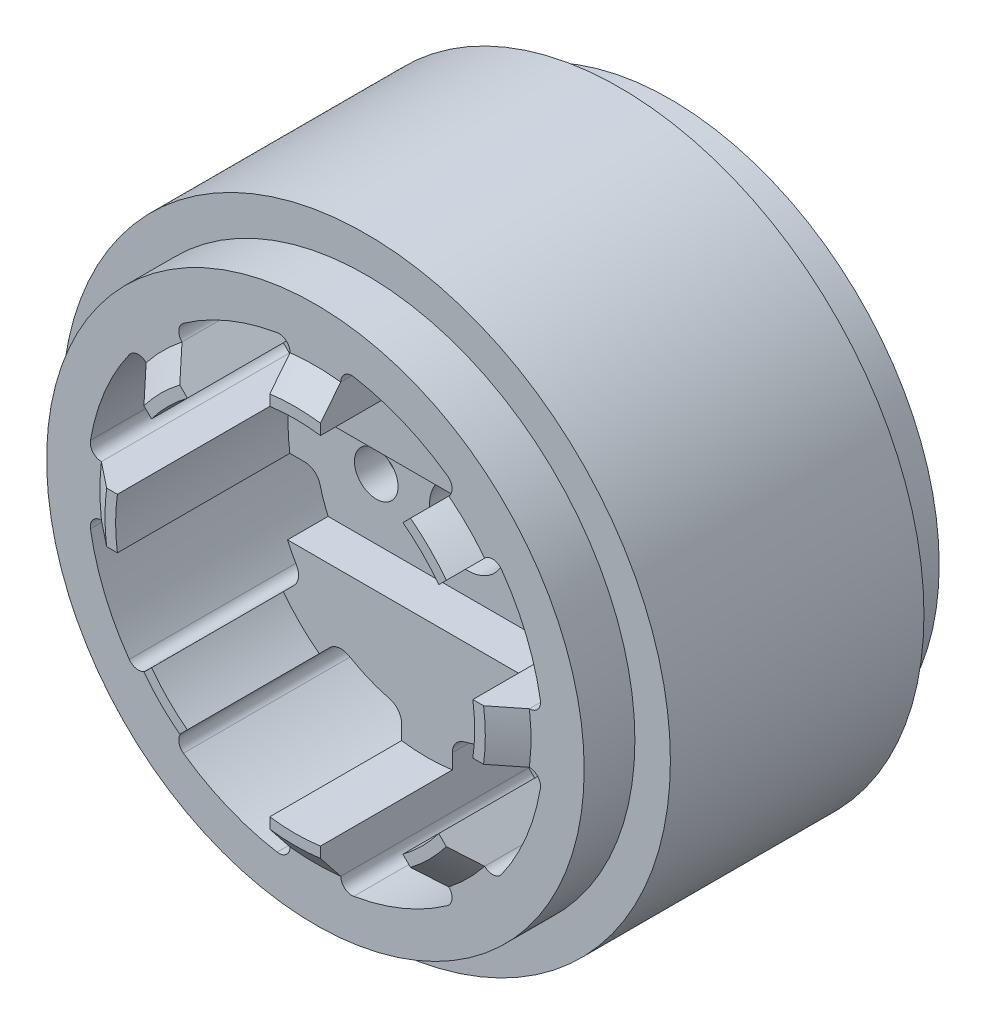
SolidWorks part; units mm, degrees
ref_plane "Front Plane" through (0, 0, 0) normal (0, 0, 1) x (1, 0, 0)
ref_plane "Top Plane" through (0, 0, 0) normal (0, 1, 0) x (1, 0, 0)
ref_plane "Right Plane" through (0, 0, 0) normal (1, 0, 0) x (0, 0, -1)
sketch "Sketch1" plane through (0, 0, 0) normal (0, 0, 1) x (1, 0, 0)
  line L0 (0, 0) -> (52.3745, 0) construction
  line L1 (0, 0) -> (0, 45.9782) construction
  line L2 (2.5, 21.1024) -> (2.5, 16.0565)
  line L3 (-13.7477, 6) -> (13.7477, 6)
  line L4 (-13.7477, -6) -> (13.7477, -6)
  line L5 (-2.5, 21.1024) -> (-2.5, 16.0565)
  line L6 (16.6894, 13.1539) -> (13.1215, 9.5859)
  line L7 (13.1539, 16.6894) -> (9.5859, 13.1215)
  line L8 (21.1024, -2.5) -> (16.0565, -2.5)
  line L9 (21.1024, 2.5) -> (16.0565, 2.5)
  line L10 (13.1539, -16.6894) -> (9.5859, -13.1215)
  line L11 (16.6894, -13.1539) -> (13.1215, -9.5859)
  line L12 (-2.5, -21.1024) -> (-2.5, -16.0565)
  line L13 (2.5, -21.1024) -> (2.5, -16.0565)
  line L14 (-16.6894, -13.1539) -> (-13.1215, -9.5859)
  line L15 (-13.1539, -16.6894) -> (-9.5859, -13.1215)
  line L16 (-21.1024, 2.5) -> (-16.0565, 2.5)
  line L17 (-21.1024, -2.5) -> (-16.0565, -2.5)
  line L18 (-13.1539, 16.6894) -> (-9.5859, 13.1215)
  line L19 (-16.6894, 13.1539) -> (-13.1215, 9.5859)
  circle A0 centre (0, 0) radius 3.75
  circle A1 centre (0, 0) radius 15
  circle A2 centre (0, 0) radius 22.5
  circle A3 centre (0, 0) radius 26.5
  circle A4 centre (9, 0) radius 3
  circle A5 centre (-9, 0) radius 3
  arc A6 (2.5, 21.1024) -> (3.7774, 22.1807) centre (3.5937, 21.1024) cw
  circle A7 centre (9, 0) radius 2.15
  circle A8 centre (-9, 0) radius 2.15
  arc A9 (-2.5, 21.1024) -> (-3.7774, 22.1807) centre (-3.5937, 21.1024) ccw
  arc A10 (16.6894, 13.1539) -> (18.3551, 13.0131) centre (17.4628, 12.3805) cw
  arc A11 (13.1539, 16.6894) -> (13.0131, 18.3551) centre (12.3805, 17.4628) ccw
  arc A12 (21.1024, -2.5) -> (22.1807, -3.7774) centre (21.1024, -3.5937) cw
  arc A13 (21.1024, 2.5) -> (22.1807, 3.7774) centre (21.1024, 3.5937) ccw
  arc A14 (13.1539, -16.6894) -> (13.0131, -18.3551) centre (12.3805, -17.4628) cw
  arc A15 (16.6894, -13.1539) -> (18.3551, -13.0131) centre (17.4628, -12.3805) ccw
  arc A16 (-2.5, -21.1024) -> (-3.7774, -22.1807) centre (-3.5937, -21.1024) cw
  arc A17 (2.5, -21.1024) -> (3.7774, -22.1807) centre (3.5937, -21.1024) ccw
  arc A18 (-16.6894, -13.1539) -> (-18.3551, -13.0131) centre (-17.4628, -12.3805) cw
  arc A19 (-13.1539, -16.6894) -> (-13.0131, -18.3551) centre (-12.3805, -17.4628) ccw
  arc A20 (-21.1024, 2.5) -> (-22.1807, 3.7774) centre (-21.1024, 3.5937) cw
  arc A21 (-21.1024, -2.5) -> (-22.1807, -3.7774) centre (-21.1024, -3.5937) ccw
  arc A22 (-13.1539, 16.6894) -> (-13.0131, 18.3551) centre (-12.3805, 17.4628) cw
  arc A23 (-16.6894, 13.1539) -> (-18.3551, 13.0131) centre (-17.4628, 12.3805) ccw
  circle A24 centre (0, 0) radius 30
  circle A25 centre (0, 0) radius 17.7
  circle A26 centre (0, 0) radius 21.25
  circle A27 centre (0, 0) radius 16.25
  arc A28 (2.5, 16.0565) -> (3.6792, 14.5418) centre (4.0625, 16.0565) ccw
  arc A29 (-2.5, 16.0565) -> (-3.6792, 14.5418) centre (-4.0625, 16.0565) cw
  arc A30 (13.1215, 9.5859) -> (12.8842, 7.681) centre (14.2263, 8.4811) ccw
  arc A31 (9.5859, 13.1215) -> (7.681, 12.8842) centre (8.4811, 14.2263) cw
  arc A32 (16.0565, -2.5) -> (14.5418, -3.6792) centre (16.0565, -4.0625) ccw
  arc A33 (16.0565, 2.5) -> (14.5418, 3.6792) centre (16.0565, 4.0625) cw
  arc A34 (9.5859, -13.1215) -> (7.681, -12.8842) centre (8.4811, -14.2263) ccw
  arc A35 (13.1215, -9.5859) -> (12.8842, -7.681) centre (14.2263, -8.4811) cw
  arc A36 (-2.5, -16.0565) -> (-3.6792, -14.5418) centre (-4.0625, -16.0565) ccw
  arc A37 (2.5, -16.0565) -> (3.6792, -14.5418) centre (4.0625, -16.0565) cw
  arc A38 (-13.1215, -9.5859) -> (-12.8842, -7.681) centre (-14.2263, -8.4811) ccw
  arc A39 (-9.5859, -13.1215) -> (-7.681, -12.8842) centre (-8.4811, -14.2263) cw
  arc A40 (-16.0565, 2.5) -> (-14.5418, 3.6792) centre (-16.0565, 4.0625) ccw
  arc A41 (-16.0565, -2.5) -> (-14.5418, -3.6792) centre (-16.0565, -4.0625) cw
  arc A42 (-9.5859, 13.1215) -> (-7.681, 12.8842) centre (-8.4811, 14.2263) ccw
  arc A43 (-13.1215, 9.5859) -> (-12.8842, 7.681) centre (-14.2263, 8.4811) cw
  point P87 (0, 0)
  point P138 (0, 0)
  dimension "D1" = 7.5
  dimension "D2" = 30
  dimension "D3" = 45
  dimension "D4" = 53
  dimension "D5" = 9
  dimension "D6" = 6
  dimension "D8" = 42.5
  dimension "D9" = 4.3
  dimension "D12" = 60
  dimension "D13" = 35.4
  dimension "D14" = 32.5
  dimension "D15" = 8
  dimension "D7" = 2.5
  dimension "D10" = 6
  dimension "D11" = 8
extrude "Boss-Extrude7" add sketch "Sketch1<15>" along normal blind 15 separate body contours A1
sketch "Sketch1<15>" plane through (0, 0, 0) normal (0, 0, 1) x (1, 0, 0) same geometry as "Sketch1"
extrude "Cut-Extrude2" cut sketch "Sketch1<16>" along normal blind 15 from surface contours A0 starting at face at (15, 0, 0)
sketch "Sketch1<16>" plane through (0, 0, 0) normal (0, 0, 1) x (1, 0, 0) same geometry as "Sketch1"
extrude "Cut-Extrude4" cut sketch "Sketch1<18>" along normal blind 12 from surface contours A5 | A4 starting at face at (3.75, 0, 0)
sketch "Sketch1<18>" plane through (0, 0, 0) normal (0, 0, 1) x (1, 0, 0) same geometry as "Sketch1"
extrude "Cut-Extrude5" cut sketch "Sketch1<19>" along normal blind 15 from surface contours A8 starting at face at (-6, 0, 0)
sketch "Sketch1<19>" plane through (0, 0, 0) normal (0, 0, 1) x (1, 0, 0) same geometry as "Sketch1"
extrude "Cut-Extrude6" cut sketch "Sketch1" along normal blind 15 from surface contours A7 starting at face at (-6, 0, 0)
extrude "Boss-Extrude12" add sketch "Sketch1<22>" along normal blind 4 from offset 15 contours L3 A1 | L4 A1 region at (0, 9.7124, 0) region at (0, -9.7124, 0)
sketch "Sketch1<22>" plane through (0, 0, 0) normal (0, 0, 1) x (1, 0, 0) same geometry as "Sketch1"
extrude "Boss-Extrude13" add sketch "Sketch1<23>" along normal blind 30 and the other way blind 5 separate body contours A3 A2 region at (-25.7505, 0, 0)
sketch "Sketch1<23>" plane through (0, 0, 0) normal (0, 0, 1) x (1, 0, 0) same geometry as "Sketch1"
extrude "Boss-Extrude14" add sketch "Sketch1<24>" along normal blind 30 and the other way blind 5 contours A26 A18 A2 A19 | A26 A20 A2 A21 | A26 A22 A2 A23 | A26 A6 A2 A9 | A26 A10 A2 A11 | A26 A12 A2 A13 | A26 A14 A2 A15 | A26 A16 A2 A17 region at (0, 21.849, 0) region at (15.4496, 15.4496, 0) region at (-15.4496, 15.4496, 0) region at (21.849, 0, 0) region at (-21.849, 0, 0) region at (15.4496, -15.4496, 0) region at (-15.4496, -15.4496, 0) region at (0, -21.849, 0)
sketch "Sketch1<24>" plane through (0, 0, 0) normal (0, 0, 1) x (1, 0, 0) same geometry as "Sketch1"
extrude "Boss-Extrude15" add sketch "Sketch1<25>" along normal blind 19 and the other way blind 5 contours L18 A25 L19 A1 | L2 A25 L5 A1 | L6 A25 L7 A1 | L10 A25 L11 A1 | L12 A25 L13 A1 | L14 A25 L15 A1 | A27 A29 A1 A28 | A27 A31 A1 A30 | A27 A43 A1 A42 | A27 A35 A1 A34 | A27 A37 A1 A36 | A27 A39 A1 A38 region at (0, 16.9131, 0) region at (0, 15.51, 0) region at (11.9594, 11.9594, 0) region at (10.9673, 10.9673, 0) region at (-11.9594, 11.9594, 0) region at (-10.9673, 10.9673, 0) region at (11.9594, -11.9594, 0) region at (-11.9594, -11.9594, 0) region at (10.9673, -10.9673, 0) region at (-10.9673, -10.9673, 0) region at (0, -16.9131, 0) region at (0, -15.51, 0)
sketch "Sketch1<25>" plane through (0, 0, 0) normal (0, 0, 1) x (1, 0, 0) same geometry as "Sketch1"
extrude "Boss-Extrude16" add sketch "Sketch1<26>" along normal blind 15 and the other way blind 5 contours L8 A25 L9 A1 | L16 A25 L17 A1 | A27 A41 A1 A40 | A27 A33 A1 A32 region at (16.9131, 0, 0) region at (15.51, 0, 0) region at (-16.9131, 0, 0) region at (-15.51, 0, 0)
sketch "Sketch1<26>" plane through (0, 0, 0) normal (0, 0, 1) x (1, 0, 0) same geometry as "Sketch1"
extrude "Boss-Extrude18" add sketch "Sketch1<28>" along normal blind 25 contours A24 A3 region at (-29.1515, 0, 0)
sketch "Sketch1<28>" plane through (0, 0, 0) normal (0, 0, 1) x (1, 0, 0) same geometry as "Sketch1"
extrude "Boss-Extrude19" add sketch "Sketch1<32>" along normal blind 32 and the other way blind 5 contours L10 A26 L11 A25 | L8 A26 L9 A25 | L6 A26 L7 A25 | L2 A26 L5 A25 | L18 A26 L19 A25 | L16 A26 L17 A25 | L14 A26 L15 A25 | L12 A26 L13 A25 region at (0, 19.4208, 0) region at (13.7326, 13.7326, 0) region at (-13.7326, 13.7326, 0) region at (19.4208, 0, 0) region at (-19.4208, 0, 0) region at (13.7326, -13.7326, 0) region at (-13.7326, -13.7326, 0) region at (0, -19.4208, 0)
sketch "Sketch1<32>" plane through (0, 0, 0) normal (0, 0, 1) x (1, 0, 0) same geometry as "Sketch1"
chamfer "Chamfer1" distance 2 distance2 2.5 8 edges at (-15.026, -15.026, 32) (-21.25, 0, 32) (-15.026, 15.026, 32) (0, 21.25, 32) (15.026, 15.026, 32) (21.25, 0, 32) (15.026, -15.026, 32) (0, -21.25, 32) first distance on face at (-14.9738, -14.9738, 31) first distance on face at (-21.1762, 0, 31) first distance on face at (-14.9738, 14.9738, 31) first distance on face at (0, 21.1762, 31) first distance on face at (14.9738, 14.9738, 31) first distance on face at (21.1762, 0, 31) first distance on face at (14.9738, -14.9738, 31) first distance on face at (0, -21.1762, 31)
chamfer "Chamfer2" distance 5 distance2 7.5 8 edges at (-10.6066, 10.6066, -5) (0, 15, -5) (10.6066, 10.6066, -5) (15, 0, -5) (10.6066, -10.6066, -5) (0, -15, -5) (-10.6066, -10.6066, -5) (-15, 0, -5) first distance on face at (-10.4446, 10.4446, -2.5) first distance on face at (0, 14.7709, -2.5) first distance on face at (10.4446, 10.4446, -2.5) first distance on face at (14.7709, 0, -2.5) first distance on face at (10.4446, -10.4446, -2.5) first distance on face at (0, -14.7709, -2.5) first distance on face at (-10.4446, -10.4446, -2.5) first distance on face at (-14.7709, 0, -2.5)
